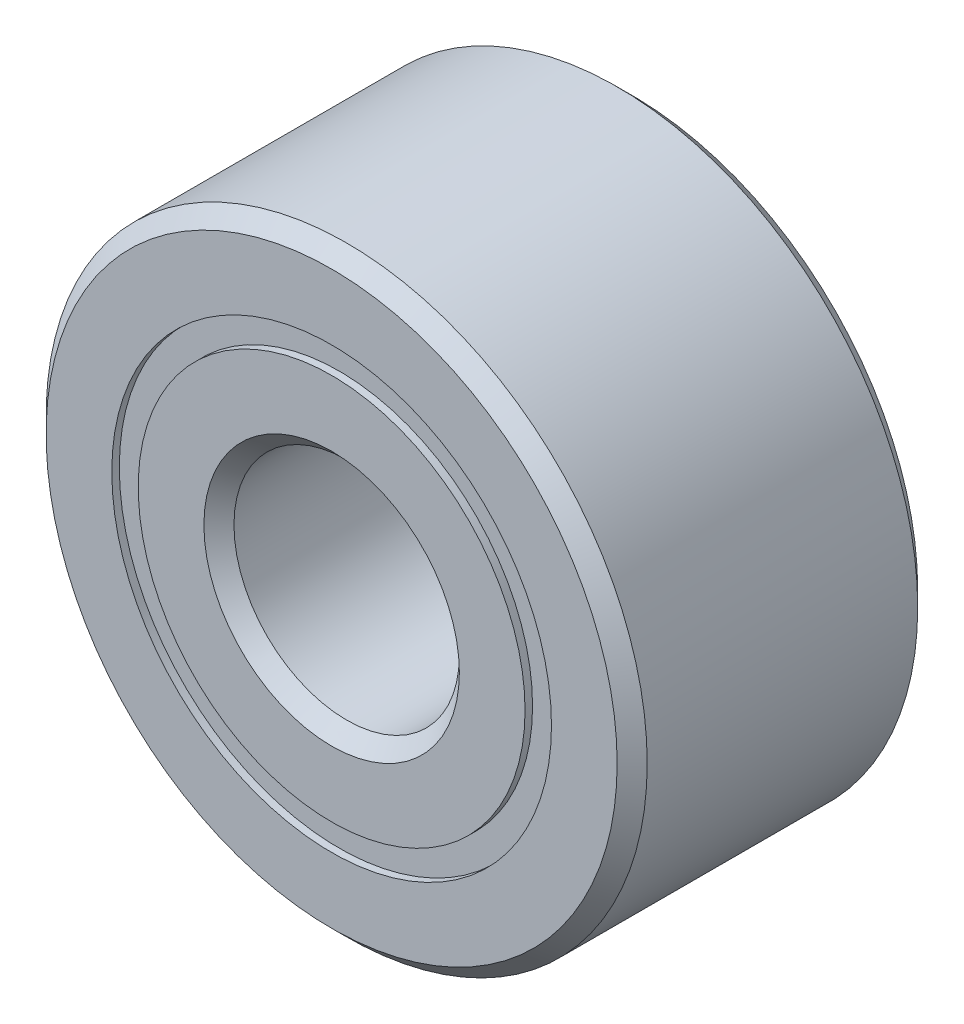
SolidWorks part; units mm, degrees
note: '?' marks a value the reader was unsure of.
ref_plane "Front Plane" through (0, 0, 0) normal (0, 0, 1) x (1, 0, 0)
ref_plane "Top Plane" through (0, 0, 0) normal (0, 1, 0) x (1, 0, 0)
ref_plane "Right Plane" through (0, 0, 0) normal (1, 0, 0) x (0, 0, -1)
sketch "Sketch1" plane through (0, 0, 0) normal (1, 0, 0) x (0, 0, -1)
  line L0 (-2, 0) -> (2, 0) construction
  line L1 (0, 4) -> (0, -4) construction
  line L2 (1.8, 4) -> (-1.8, 4)
  line L3 (-1.8, 4) -> (-2, 3.8)
  line L4 (-2, 3.8) -> (-2, 2.9258)
  line L5 (-2, 2.9258) -> (-0.8889, 2.9258)
  line L6 (2, 2.9258) -> (0.8889, 2.9258)
  line L7 (2, 3.8) -> (2, 2.9258)
  line L8 (1.8, 4) -> (2, 3.8)
  line L9 (0, 4) -> (0, 2.75) construction
  line L10 (0, 2.75) -> (0, 1.5) construction
  arc A0 (-0.8889, 2.9258) -> (0.8889, 2.9258) centre (0, 2.75) cw
  point P14 (0, 1.5)
  dimension "Width" = 4
  dimension "OD" = 8
  dimension "D1" = 45
  dimension "D2" = 0.2
  dimension "Shaft Dia" = 3
  dimension "D3" = 1.7778
  dimension "D4" = 0.1758
revolve "Revolve1" add sketch "Sketch1" angle 360 about L0
sketch "Sketch3" plane through (0, 0, 0) normal (1, 0, 0) x (0, 0, -1)
  line L0 (-2, 2.5742) -> (-0.8889, 2.5742)
  line L1 (0, 4) -> (0, -4) construction
  line L2 (-2, 3.8) -> (-2, 2.9258) construction
  line L3 (-2, 2.5742) -> (-2, 1.7)
  line L4 (-1.8, 4) -> (-2, 3.8) construction
  line L5 (-2, 1.7) -> (-1.8, 1.5)
  line L6 (-1.8, 1.5) -> (1.8, 1.5)
  line L7 (1.8, 4) -> (1.8, -4) construction
  line L8 (1.8, 1.5) -> (2, 1.7)
  line L9 (2, -3.8) -> (2, 3.8) construction
  line L10 (2, 1.7) -> (2, 2.5742)
  line L11 (2, 2.5742) -> (0.8889, 2.5742)
  line L13 (1.8, 4) -> (2, 3.8) construction
  arc A0 (0.8889, 2.9258) -> (-0.8889, 2.9258) centre (0, 2.75) ccw construction
  arc A1 (0.8889, 2.5742) -> (-0.8889, 2.5742) centre (0, 2.75) cw
revolve "Revolve3" add sketch "Sketch3" angle 360 about L0
sketch "Sketch4" plane through (0, 0, 0) normal (1, 0, 0) x (0, 0, -1)
  line L0 (-0.9061, 2.75) -> (0.9061, 2.75)
  arc A2 (-0.9061, 2.75) -> (0.9061, 2.75) centre (0, 2.75) cw
  arc A3 (0.8889, 2.9258) -> (-0.8889, 2.9258) centre (0, 2.75) ccw construction
revolve "Revolve4" add sketch "Sketch4" angle 360 about L0
ref_axis "Axis1" through (0, 0, -2) along (0, 0, 1)?
pattern_circular "CirPattern1" count 12 every 30 about axis through (0, 0, 0) along (0, 0, 1) of bodies 104
sketch "Sketch5" plane through (0, 0, 0) normal (1, 0, 0) x (0, 0, -1)
  line L0 (-2, 2.9258) -> (-0.8889, 2.9258) construction
  line L1 (-1.9, 2.9258) -> (-0.9061, 2.9258)
  line L2 (-1.9, 2.9258) -> (-1.9, 2.5742)
  line L3 (-1.9, 2.5742) -> (-0.9061, 2.5742)
  line L4 (-0.9061, 2.9258) -> (-0.9061, 2.5742)
  line L5 (-2, 2.5742) -> (-0.8889, 2.5742) construction
  line L6 (2, 2.9258) -> (0.8889, 2.9258) construction
  line L7 (1.9, 2.9258) -> (0.9061, 2.9258)
  line L8 (1.9, 2.9258) -> (1.9, 2.5742)
  line L9 (1.9, 2.5742) -> (0.9061, 2.5742)
  line L10 (0.9061, 2.9258) -> (0.9061, 2.5742)
  line L11 (2, 2.5742) -> (0.8889, 2.5742) construction
  line L12 (-1.8, 4) -> (-2, 3.8) construction
  point P18 (-1.9, 3.9)
revolve "Revolve5" add sketch "Sketch5" angle 360 about L0
sketch "Sketch6" plane through (0, 0, 0) normal (1, 0, 0) x (0, 0, -1)
  line L0 (2, 0) -> (-2, 0) construction
  line L1 (2, 2.9258) -> (1.2126, 2.9258)
  line L2 (2, 2.9258) -> (2, 6.9469)
  line L3 (2, 6.9469) -> (1.2126, 6.9469)
  line L4 (1.2126, 2.9258) -> (1.2126, 6.9469)
  dimension "Th" = 0.7874
  dimension "Flange OD" = 13.8938
equation "\"D2@Sketch1\" = \"Width@Sketch1\"*.05"
equation "\"D3@Sketch1\" = \"Width@Sketch1\"/2.25"
equation "\"D4@Sketch1\" = (((\"OD@Sketch1\"-\"Width@Sketch1\")/2)/3.25)/3.5"
equation "\"D2@CirPattern1\" = 360/\"Balls@CirPattern1\""
